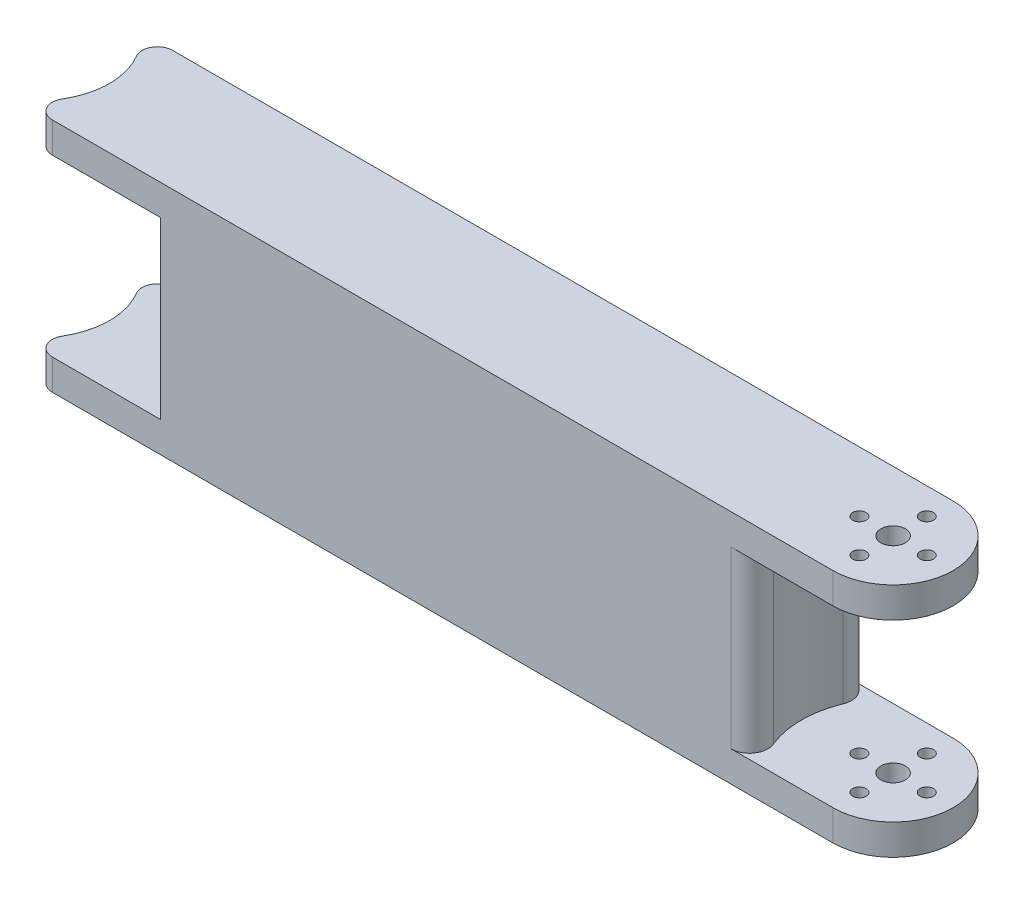
SolidWorks part; units mm, degrees
ref_plane "Front Plane" through (0, 0, 0) normal (0, 0, 1) x (1, 0, 0)
ref_plane "Top Plane" through (0, 0, 0) normal (0, 1, 0) x (1, 0, 0)
ref_plane "Right Plane" through (0, 0, 0) normal (1, 0, 0) x (0, 0, -1)
sketch "Sketch1" plane through (0, 0, 0) normal (0, 1, 0) x (1, 0, 0)
  line L0 (0, 0) -> (177.8, 0) construction
  line L1 (-55, 0) -> (55, 0) construction
  line L2 (0, 12.5) -> (177.8, 12.5)
  line L3 (0, -12.5) -> (177.8, -12.5)
  line L4 (88.9, 12.5) -> (88.9, -12.5) construction
  line L5 (-33.2205, 0) -> (214.1012, 0) construction
  arc A0 (0, 12.5) -> (0, -12.5) centre (0, 0) ccw
  arc A1 (177.8, -12.5) -> (177.8, 12.5) centre (177.8, 0) ccw
  circle A2 centre (0, 0) radius 7 construction
  circle A3 centre (-7, 0) radius 1.397 construction
  circle A4 centre (0, 0) radius 2.54 construction
  circle A5 centre (0, 7) radius 1.397 construction
  circle A6 centre (7, 0) radius 1.397 construction
  circle A7 centre (0, -7) radius 1.397 construction
  circle A8 centre (177.8, 7) radius 1.397
  circle A9 centre (184.8, 0) radius 1.397
  circle A10 centre (177.8, -7) radius 1.397
  circle A11 centre (177.8, 0) radius 2.54
  circle A12 centre (170.8, 0) radius 1.397
  point P5 (88.9, 0)
  point P23 (0, 0)
  dimension "D3" = 14
  dimension "D4" = 2.794
  dimension "D5" = 5.08
  dimension "D1" = 177.8
  dimension "D2" = 25
  dimension "D6" = 4
extrude "Boss-Extrude1" add sketch "Sketch1" along normal blind 6.35
sketch "Sketch2" plane through (0, 6.35, 0) normal (0, 1, 0) x (1, 0, 0)
  line L0 (88.9, 12.5) -> (88.9, -12.5) construction
  line L1 (177.8, 12.5) -> (0, 12.5) construction
  line L2 (0, -12.5) -> (177.8, -12.5) construction
  line L3 (0, 12.5) -> (177.8, 12.5)
  line L4 (38.1, 12.5) -> (156.6489, 12.5)
  line L5 (177.8, -12.5) -> (0, -12.5)
  line L6 (156.6489, -12.5) -> (38.1, -12.5)
  line L7 (38.1, 12.5) -> (38.1, -12.5)
  arc A1 (177.8, -12.5) -> (177.8, 12.5) centre (177.8, 0) ccw
  arc A3 (0, 12.5) -> (0, -12.5) centre (0, 0) ccw
  arc A5 (160.1778, -7.2361) -> (160.1778, 7.2361) centre (177.8, 0) cw
  arc A8 (160.1778, 7.2361) -> (156.6489, 12.5) centre (156.6489, 8.6851) ccw
  arc A9 (160.1778, -7.2361) -> (156.6489, -12.5) centre (156.6489, -8.6851) cw
  point P20 (14.3754, -12.5)
  point P23 (14.3754, 12.5)
  point P26 (163.4246, 12.5)
  point P29 (163.4246, -12.5)
  dimension "D1" = 38.1
extrude "Boss-Extrude2" add sketch "Sketch2" along normal blind 18.161 contours L4 A8 A5 A9 L6 L7
mirror "Mirror1" about plane through (156.6489, 24.511, 8.6851) normal (0, -1, 0) of "Boss-Extrude2"
sketch "Sketch3" plane through (0, 42.672, 0) normal (0, 1, 0) x (1, 0, 0)
  line L0 (0, 12.5) -> (177.8, 12.5)
  line L1 (15.6005, 12.5) -> (177.8, 12.5)
  line L2 (177.8, -12.5) -> (0, -12.5)
  line L3 (177.8, -12.5) -> (15.6005, -12.5)
  arc A0 (177.8, -12.5) -> (177.8, 12.5) centre (177.8, 0) ccw
  arc A1 (177.8, -12.5) -> (177.8, 12.5) centre (177.8, 0) ccw
  arc A2 (0, 12.5) -> (0, -12.5) centre (0, 0) ccw
  circle A4 centre (170.8, 0) radius 1.397
  circle A6 centre (177.8, 0) radius 2.54
  circle A8 centre (170.8, 0) radius 1.397
  circle A10 centre (177.8, 0) radius 2.54
  circle A12 centre (177.8, -7) radius 1.397
  arc A14 (12.8752, -7.696) -> (12.8752, 7.696) centre (0, 0) ccw
  arc A16 (12.8752, -7.696) -> (15.6005, -12.5) centre (15.6005, -9.325) ccw
  arc A18 (12.8752, 7.696) -> (15.6005, 12.5) centre (15.6005, 9.325) cw
  circle A24 centre (184.8, 0) radius 1.397
  circle A25 centre (177.8, 7) radius 1.397
  circle A26 centre (177.8, -7) radius 1.397
  circle A27 centre (184.8, 0) radius 1.397
  circle A28 centre (177.8, 7) radius 1.397
  dimension "D1" = 30
  dimension "D2" = 3.175
extrude "Boss-Extrude3" add sketch "Sketch3" along normal blind 6.35
sketch "Sketch4" plane through (0, 6.35, 0) normal (0, 1, 0) x (1, 0, 0)
  line L3 (38.1, -12.5) -> (38.1, 12.5)
  line L4 (38.1, 12.5) -> (0, 12.5)
  line L5 (0, -12.5) -> (38.1, -12.5)
  line L7 (15.6005, 12.5) -> (0, 12.5)
  line L8 (0, -12.5) -> (15.6005, -12.5)
  arc A0 (12.8752, -7.696) -> (12.8752, 7.696) centre (0, 0) ccw construction
  arc A1 (0, 12.5) -> (0, -12.5) centre (0, 0) ccw
  arc A2 (0, 12.5) -> (0, -12.5) centre (0, 0) ccw
  arc A3 (12.8752, -7.696) -> (12.8752, 7.696) centre (0, 0) ccw
  arc A4 (12.8752, -7.696) -> (15.6005, -12.5) centre (15.6005, -9.325) ccw construction
  arc A5 (15.6005, 12.5) -> (12.8752, 7.696) centre (15.6005, 9.325) ccw construction
  arc A6 (12.8752, -7.696) -> (15.6005, -12.5) centre (15.6005, -9.325) ccw
  arc A7 (15.6005, 12.5) -> (12.8752, 7.696) centre (15.6005, 9.325) ccw
  dimension "D1" = 0
extrude "Cut-Extrude1" cut sketch "Sketch4" against normal blind 6.35
